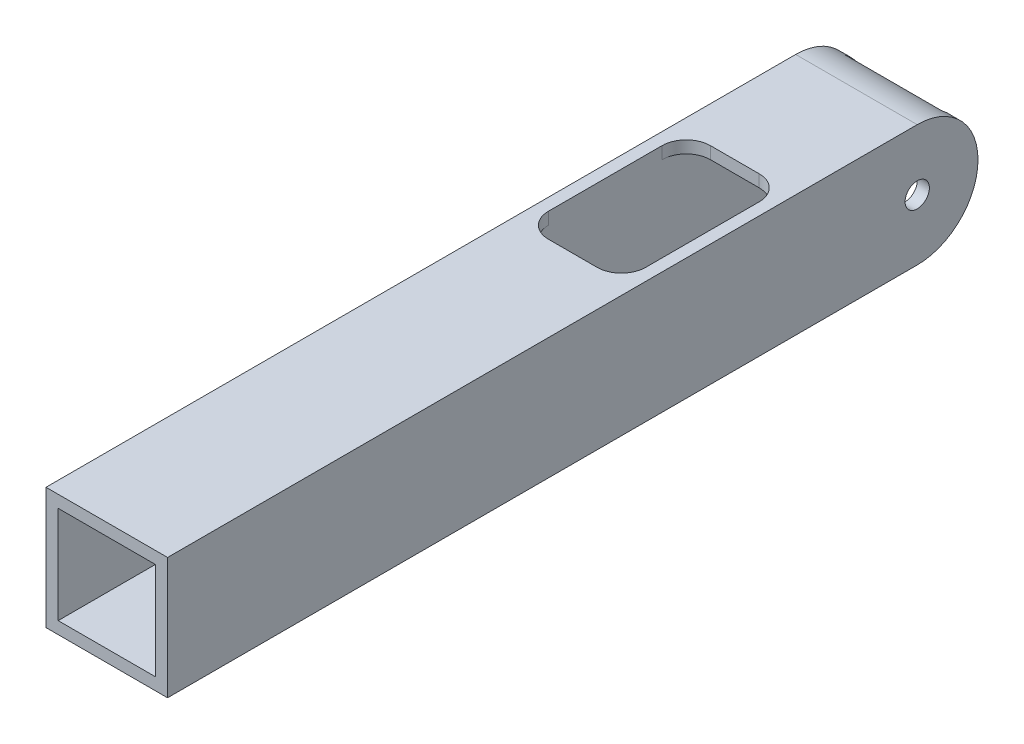
SolidWorks part; units mm, degrees
ref_plane "Plan de face" through (0, 0, 0) normal (0, 0, 1) x (1, 0, 0)
ref_plane "Plan de dessus" through (0, 0, 0) normal (0, 1, 0) x (1, 0, 0)
ref_plane "Plan de droite" through (0, 0, 0) normal (1, 0, 0) x (0, 0, -1)
sketch "Esquisse1" plane through (0, 0, 0) normal (0, 0, 1) x (1, 0, 0)
  line L1 (-7.5, -7.5) -> (7.5, -7.5)
  line L2 (-7.5, -7.5) -> (-7.5, 7.5)
  line L3 (-7.5, 7.5) -> (7.5, 7.5)
  line L4 (7.5, -7.5) -> (7.5, 7.5)
  line L5 (-7.5, -7.5) -> (7.5, 7.5) construction
  line L6 (-7.5, 7.5) -> (7.5, -7.5) construction
  point P0 (0, 0)
  dimension "D1" = 15
  dimension "D2" = 15
extrude "Extrusion1" add sketch "Esquisse1" along normal blind 100
sketch "Esquisse2" plane through (0, 0, 100) normal (0, 0, 1) x (1, 0, 0)
  line L0 (7.5, 7.5) -> (-7.5, 7.5) construction
  line L1 (-6, -6) -> (6, -6)
  line L2 (-6, -6) -> (-6, 6)
  line L3 (-6, 6) -> (6, 6)
  line L4 (6, -6) -> (6, 6)
  line L5 (-6, -6) -> (6, 6) construction
  line L6 (-6, 6) -> (6, -6) construction
  line L7 (7.5, -7.5) -> (7.5, 7.5) construction
  point P0 (0, 0)
  dimension "D1" = 1.5
  dimension "D2" = 1.5
extrude "Extrusion2" cut sketch "Esquisse2" against normal through all
fillet "Congé1" radius 7.5 2 edges at (0, -7.5, 0) (0, 7.5, 0)
sketch "Esquisse3" plane through (7.5, 0, 0) normal (1, 0, 0) x (0, 0, -1)
  circle A0 centre (-7.5, 0) radius 1.5
  arc A1 (0, 0) -> (-7.5, 7.5) centre (-7.5, 0) ccw construction
  dimension "D1" = 3
extrude "Extrusion3" cut sketch "Esquisse3" against normal through all
sketch "Esquisse4" plane through (0, 7.5, 0) normal (0, 1, 0) x (-1, 0, 0)
  line L0 (-7.5, 7.5) -> (7.5, 7.5) construction
  line L1 (-6, 42.5) -> (6, 42.5)
  line L2 (-6, 42.5) -> (-6, 22.5)
  line L3 (-6, 22.5) -> (6, 22.5)
  line L4 (6, 42.5) -> (6, 22.5)
  line L5 (-6, 42.5) -> (6, 22.5) construction
  line L6 (-6, 22.5) -> (6, 42.5) construction
  line L7 (7.5, 100) -> (7.5, 7.5) construction
  point P0 (0, 32.5)
  dimension "D1" = 20
  dimension "D2" = 12
  dimension "D3" = 25
  dimension "D4" = 7.5
extrude "Enlèv. mat.-Extru.1" cut sketch "Esquisse4" against normal blind 3
fillet "Congé2" radius 3 4 edges at (6, 6.75, 22.5) (-6, 6.75, 22.5) (6, 6.75, 42.5) (-6, 6.75, 42.5)
